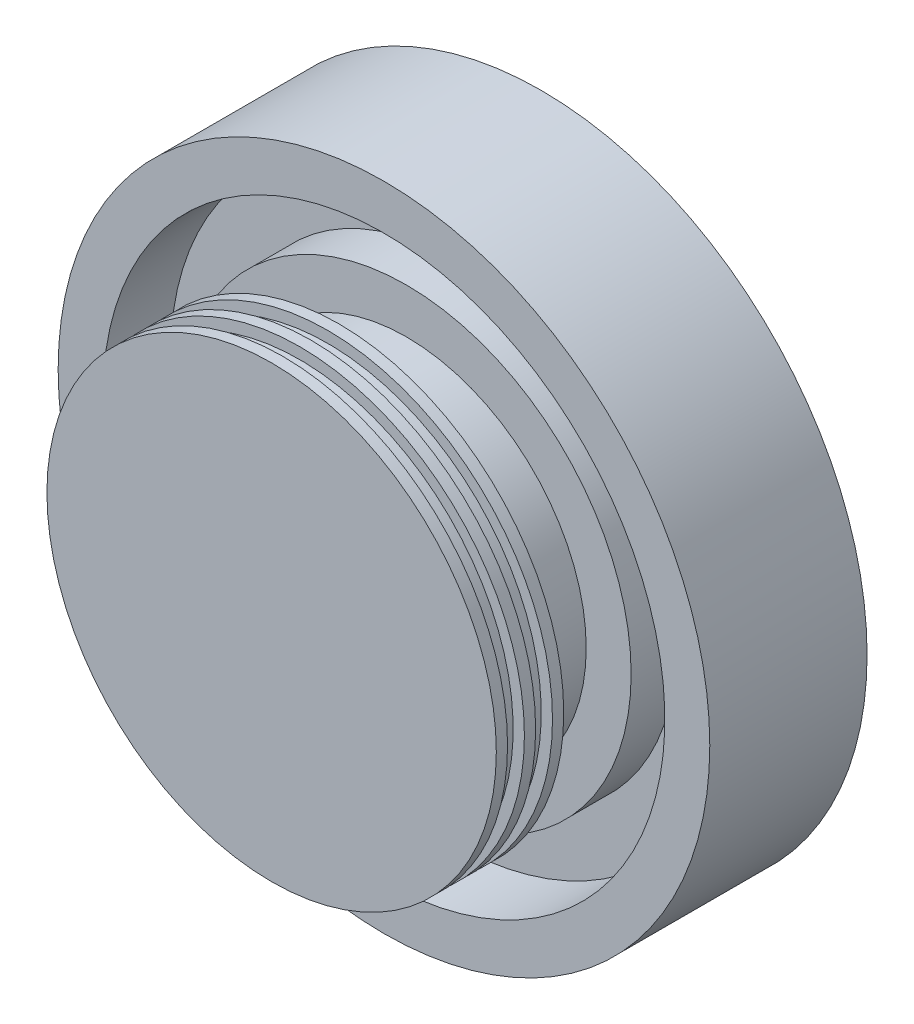
SolidWorks part; units mm, degrees
material "6061 Alloy"
ref_plane "Front Plane" through (0, 0, 0) normal (0, 0, 1) x (1, 0, 0)
ref_plane "Top Plane" through (0, 0, 0) normal (0, 1, 0) x (1, 0, 0)
ref_plane "Right Plane" through (0, 0, 0) normal (1, 0, 0) x (0, 0, -1)
sketch "Sketch1" plane through (0, 0, 0) normal (0, 1, 0) x (1, 0, 0)
  line L0 (0, 0) -> (63.5, 0)
  line L1 (63.5, 0) -> (63.5, 3.175)
  line L2 (63.5, 3.175) -> (60.325, 3.175)
  line L3 (60.325, 3.175) -> (60.325, 7.9375)
  line L4 (60.325, 7.9375) -> (63.5, 7.9375)
  line L5 (63.5, 7.9375) -> (63.5, 11.1125)
  line L6 (63.5, 11.1125) -> (60.325, 11.1125)
  line L7 (60.325, 11.1125) -> (60.325, 15.875)
  line L8 (60.325, 15.875) -> (63.5, 15.875)
  line L9 (63.5, 15.875) -> (63.5, 19.05)
  line L10 (63.5, 19.05) -> (50.8, 19.05)
  line L11 (50.8, 19.05) -> (50.8, 38.1)
  line L12 (50.8, 38.1) -> (63.5, 38.1)
  line L13 (63.5, 38.1) -> (63.5, 50.8)
  line L14 (63.5, 50.8) -> (79.375, 50.8)
  line L15 (79.375, 50.8) -> (79.375, 31.75)
  line L24 (79.375, 31.75) -> (92.075, 31.75)
  line L25 (92.075, 31.75) -> (92.075, 76.2)
  line L28 (12.7, 76.2) -> (12.7, 63.5)
  line L29 (12.7, 63.5) -> (38.1, 63.5)
  line L30 (38.1, 63.5) -> (38.1, 44.45)
  line L31 (38.1, 44.45) -> (0, 44.45)
  line L32 (0, 44.45) -> (0, 0)
  line L33 (12.7, 76.2) -> (92.075, 76.2)
  point P19 (0, 0)
  dimension "D1" = 63.5
  dimension "D2" = 15.875
  dimension "D3" = 3.175
  dimension "D4" = 4.7625
  dimension "D5" = 3.175
  dimension "D6" = 19.05
  dimension "D7" = 12.7
  dimension "D8" = 12.7
  dimension "D9" = 12.7
  dimension "D10" = 12.7
  dimension "D11" = 76.2
  dimension "D12" = 38.1
  dimension "D13" = 12.7
  dimension "D14" = 19.05
  dimension "D15" = 19.05
revolve "Revolve1" add sketch "Sketch1" angle 360 about L32 region at (43.0967, 0, -39.3328)
